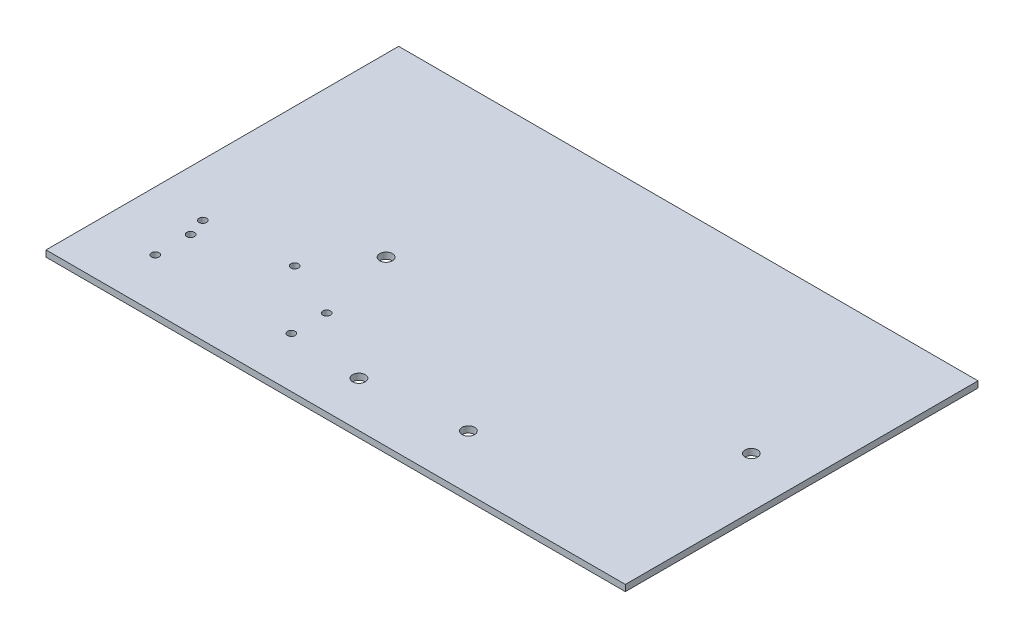
SolidWorks part; units mm, degrees
ref_plane "Front Plane" through (0, 0, 0) normal (0, 0, 1) x (1, 0, 0)
ref_plane "Top Plane" through (0, 0, 0) normal (0, 1, 0) x (1, 0, 0)
ref_plane "Right Plane" through (0, 0, 0) normal (1, 0, 0) x (0, 0, -1)
sketch "Sketch1" plane through (0, 0, 0) normal (0, 1, 0) x (1, 0, 0)
  line L1 (-158.75, 88.9) -> (158.75, 88.9)
  line L2 (-158.75, 88.9) -> (-158.75, -88.9)
  line L3 (-158.75, -88.9) -> (158.75, -88.9)
  line L4 (158.75, 88.9) -> (158.75, -88.9)
  line L5 (-158.75, 88.9) -> (158.75, -88.9) construction
  line L6 (-158.75, -88.9) -> (158.75, 88.9) construction
  circle A0 centre (-69.85, -6.35) radius 3.175
  circle A1 centre (107.95, 0) radius 3.175
  circle A4 centre (-129.032, -45.72) radius 1.905
  circle A5 centre (-60.452, -45.72) radius 1.905
  circle A7 centre (-129.032, -63.5) radius 1.905
  circle A8 centre (-60.452, -63.5) radius 1.905
  point P0 (0, 0)
  dimension "D3" = 6.35
  dimension "D4" = 6.35
  dimension "D14" = 3.81
  dimension "D17" = 17.78
  dimension "D1" = 317.5
  dimension "D2" = 177.8
  dimension "D5" = 88.9
  dimension "D6" = 266.7
  dimension "D7" = 88.9
  dimension "D8" = 82.55
  dimension "D13" = 29.718
  dimension "D15" = 68.58
  dimension "D16" = 25.4
extrude "Boss-Extrude1" add sketch "Sketch1" along normal blind 3.175
sketch "Sketch2" plane through (0, 3.175, 0) normal (0, 1, 0) x (1, 0, 0)
  line L0 (-158.75, 88.9) -> (-158.75, -88.9) construction
  line L1 (-158.75, -88.9) -> (158.75, -88.9) construction
  circle A0 centre (-89.0817, -33.177) radius 1.905
  circle A1 centre (-132.1376, -36.4483) radius 1.905
  dimension "D1" = 3.81
  dimension "D2" = 69.6683
  dimension "D3" = 52.4517
  dimension "D4" = 55.723
  dimension "D5" = 43.18
extrude "Cut-Extrude1" cut sketch "Sketch2" against normal through all
sketch "Sketch3" plane through (0, 0, 0) normal (0, -1, 0) x (-1, 0, 0)
  line L0 (158.75, -88.9) -> (-158.75, -88.9) construction
  line L1 (158.75, 88.9) -> (158.75, -88.9) construction
  circle A0 centre (23.8295, -66.04) radius 3.175
  circle A1 centre (-26.7643, -61.468) radius 3.175
  dimension "D1" = 6.35
  dimension "D2" = 4.572
  dimension "D3" = 22.86
  dimension "D4" = 185.5143
  dimension "D5" = 50.8
extrude "Cut-Extrude2" cut sketch "Sketch3" against normal through all
sketch "Sketch4" plane through (0, 3.175, 0) normal (0, 1, 0) x (1, 0, 0)
  line L0 (-158.75, -88.9) -> (158.75, -88.9) construction
  line L1 (158.75, 88.9) -> (133.35, 88.9)
  line L2 (158.75, 88.9) -> (158.75, -88.9)
  line L3 (158.75, -88.9) -> (133.35, -88.9)
  line L4 (133.35, 88.9) -> (133.35, -88.9)
  dimension "D1" = 25.4
extrude "Cut-Extrude3" cut sketch "Sketch4" against normal through all
